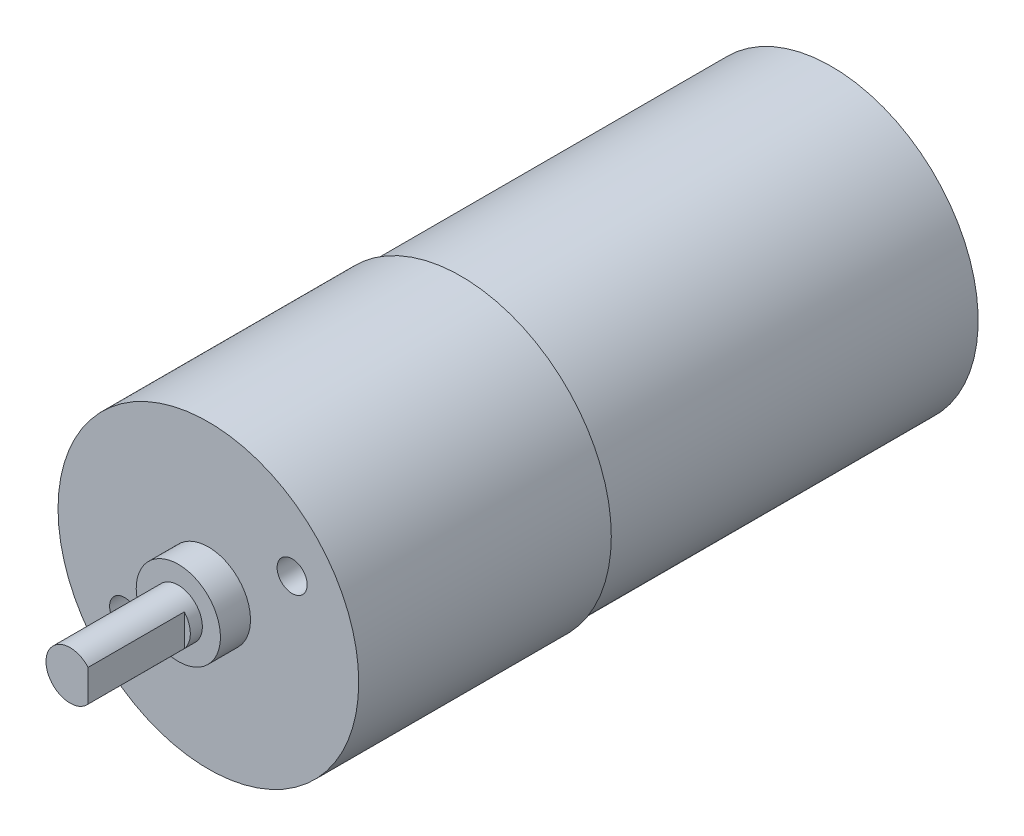
SolidWorks part; units mm, degrees
ref_plane "Front Plane" through (0, 0, 0) normal (1, 0, 0) x (0, 1, 0)
ref_plane "Gearbox Face" through (0, 0, 0) normal (0, 0, 1) x (0, 1, 0)
ref_plane "Right Plane" through (0, 0, 0) normal (0, 1, 0) x (-1, 0, 0)
sketch "Sketch1" plane through (0, 0, 0) normal (0, 1, 0) x (-1, 0, 0)
  line L0 (0, 11.5) -> (-2, 11.5)
  line L1 (-2, 11.5) -> (-2, 2.5)
  line L2 (-2, 2.5) -> (-3.5, 2.5)
  line L3 (-3.5, 2.5) -> (-3.5, 0)
  line L4 (-3.5, 0) -> (-12.5, 0)
  line L5 (-12.5, 0) -> (-12.5, -21)
  line L6 (-12.5, -21) -> (-12.2, -21)
  line L7 (-12.2, -21) -> (-12.2, -51.8)
  line L8 (-12.2, -51.8) -> (0, -51.8)
  line L9 (0, -51.8) -> (0, 11.5)
  line L10 (0, -60) -> (0, 20) construction
revolve "Motor Body" add sketch "Sketch1" angle 360 about L10
sketch "Sketch2" plane through (0, 0, 0) normal (0, 1, 0) x (-1, 0, 0)
  line L1 (-1.5, 3.5) -> (-3, 3.5)
  line L2 (-1.5, 3.5) -> (-1.5, 12)
  line L3 (-1.5, 12) -> (-3, 12)
  line L4 (-3, 3.5) -> (-3, 12)
extrude "Shaft D-Flat" cut sketch "Sketch2" against normal through all and the other way through all
sketch "Sketch3" plane through (0, 0, 0) normal (0, 0, 1) x (0, 1, 0)
  circle A0 centre (4.8754, -6.9628) radius 1.25
  circle A1 centre (-4.8754, 6.9628) radius 1.25
extrude "M3 Mounting Holes" cut sketch "Sketch3" against normal blind 3.5
ref_axis "Shaft Axis" through (0, 0, -54.965) along (0, 0, 1)
